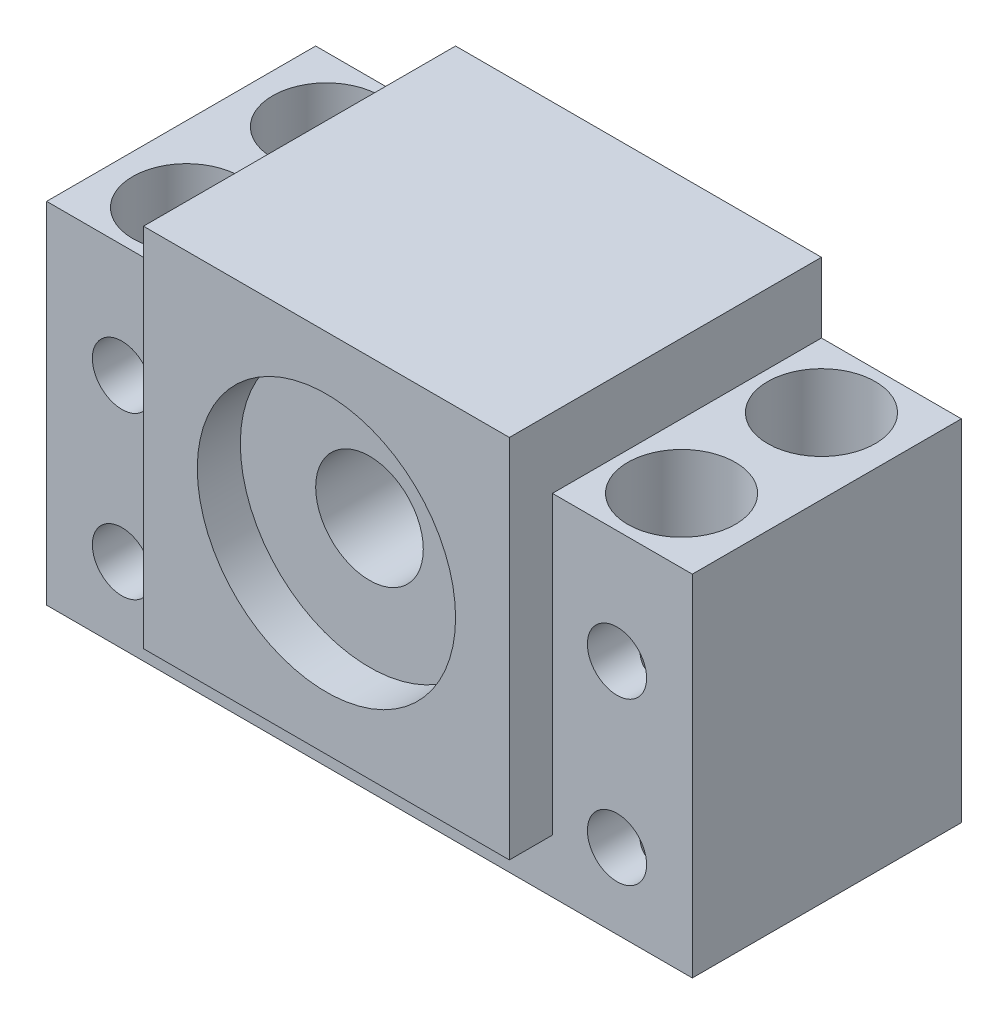
SolidWorks part; units mm, degrees
ref_plane "Спереди" through (0, 0, 0) normal (0, 0, 1) x (1, 0, 0)
ref_plane "Сверху" through (0, 0, 0) normal (0, 1, 0) x (1, 0, 0)
ref_plane "Справа" through (0, 0, 0) normal (1, 0, 0) x (0, 0, -1)
sketch "Эскиз1" plane through (0, 0, 0) normal (0, 0, 1) x (1, 0, 0)
  line L1 (0, 0) -> (60, 0)
  line L2 (0, 0) -> (0, 32.5)
  line L3 (0, 32.5) -> (60, 32.5)
  line L4 (60, 0) -> (60, 32.5)
  dimension "D1" = 32.5
  dimension "D2" = 60
extrude "Бобышка-Вытянуть1" add sketch "Эскиз1" along normal blind 25
sketch "Эскиз2" plane through (0, 0, 25) normal (0, 0, 1) x (1, 0, 0)
  line L0 (30, 0) -> (30, 41.6378) construction
  line L1 (13, 5) -> (47, 5)
  line L2 (13, 5) -> (13, 39)
  line L3 (13, 39) -> (47, 39)
  line L4 (47, 5) -> (47, 39)
  line L5 (0, 0) -> (60, 0) construction
  point P8 (30, 5)
  dimension "D1" = 39
  dimension "D2" = 34
extrude "Бобышка-Вытянуть2" add sketch "Эскиз2" against normal up to surface (25 mm away) up to face at (30, 16.25, 0)
extrude "Бобышка-Вытянуть3" add sketch "Эскиз2<2>" along normal blind 42
sketch "Эскиз2<2>" plane through (0, 0, 25) normal (0, 0, 1) x (1, 0, 0) same geometry as "Эскиз2"
sketch "Эскиз3" plane through (47, 0, 0) normal (1, 0, 0) x (0, 0, -1)
  line L0 (-67, 5) -> (-67, 39) construction
  line L1 (-67, 39) -> (-29, 39)
  line L2 (-67, 39) -> (-67, 5)
  line L3 (-67, 5) -> (-29, 5)
  line L4 (-29, 39) -> (-29, 5)
  line L5 (-67, 5) -> (-25, 5) construction
  line L6 (0, 39) -> (-67, 39) construction
  line L7 (0, 32.5) -> (0, 39) construction
  point P12 (0, 35.75)
  dimension "D1" = 29
extrude "Вырез-Вытянуть1" cut sketch "Эскиз3" against normal through all
sketch "Эскиз4" plane through (0, 0, 25) normal (0, 0, 1) x (1, 0, 0)
  line L0 (0, 22) -> (60, 22) construction
  line L1 (0, 32.5) -> (0, 0) construction
  line L2 (60, 0) -> (60, 32.5) construction
  line L3 (0, 0) -> (60, 0) construction
  line L4 (0, 7) -> (60, 7) construction
  line L5 (30, 39) -> (30, 0) construction
  line L6 (13, 39) -> (47, 39) construction
  line L7 (7, 32.5) -> (7, 0) construction
  line L8 (13, 32.5) -> (0, 32.5) construction
  line L9 (53, 32.5) -> (53, 0) construction
  line L10 (60, 32.5) -> (47, 32.5) construction
  circle A0 centre (7, 22) radius 2.75
  circle A1 centre (7, 7) radius 2.75
  circle A2 centre (53, 7) radius 2.75
  circle A3 centre (53, 22) radius 2.75
  dimension "D4" = 5.5
  dimension "D1" = 22
  dimension "D2" = 15
  dimension "D3" = 46
extrude "Вырез-Вытянуть2" cut sketch "Эскиз4" against normal through all
sketch "Эскиз5" plane through (0, 32.5, 0) normal (0, 1, 0) x (1, 0, 0)
  line L0 (4.25, -25) -> (9.75, -25) construction
  line L1 (4.25, -25) -> (9.75, -25) construction
  line L2 (50.25, -25) -> (55.75, -25) construction
  line L3 (50.25, -25) -> (55.75, -25) construction
  line L4 (7, -25) -> (7, 0) construction
  line L5 (13, 0) -> (0, 0) construction
  line L6 (53, -25) -> (53, 0) construction
  line L7 (0, -6) -> (60, -6) construction
  line L8 (0, -25) -> (0, 0) construction
  line L9 (60, -25) -> (60, 0) construction
  line L10 (0, -19) -> (60, -19) construction
  line L11 (9.75, -25) -> (9.75, 0) construction
  line L12 (50.25, -25) -> (50.25, 0) construction
  line L13 (60, 0) -> (47, 0) construction
  circle A0 centre (7, -19) radius 2.75
  circle A1 centre (7, -6) radius 2.75
  circle A2 centre (53, -6) radius 2.75
  circle A3 centre (53, -19) radius 2.75
  dimension "D1" = 6
  dimension "D2" = 13
extrude "Вырез-Вытянуть3" cut sketch "Эскиз5" against normal through all
sketch "Эскиз6" plane through (0, 32.5, 0) normal (0, 1, 0) x (1, 0, 0)
  circle A0 centre (7, -6) radius 5
  circle A1 centre (7, -19) radius 5
  circle A3 centre (53, -19) radius 5
  circle A4 centre (53, -6) radius 5
  dimension "D1" = 10
extrude "Вырез-Вытянуть4" cut sketch "Эскиз6" against normal blind 7.5
sketch "Эскиз7" plane through (0, 0, 29) normal (0, 0, 1) x (1, 0, 0)
  line L0 (30, 39) -> (30, 5) construction
  line L1 (13, 39) -> (47, 39) construction
  line L2 (13, 5) -> (47, 5) construction
  line L3 (0, 0) -> (60, 0) construction
  circle A0 centre (30, 22) radius 5
  point P10 (30, 0)
  dimension "D1" = 22
  dimension "D2" = 10
extrude "Вырез-Вытянуть5" cut sketch "Эскиз7" against normal through all
sketch "Эскиз8" plane through (0, 0, 29) normal (0, 0, 1) x (1, 0, 0)
  circle A1 centre (30, 22) radius 12
  dimension "D1" = 24
extrude "Вырез-Вытянуть6" cut sketch "Эскиз8" against normal up to surface (4 mm away) up to face at (9.75, 7, 25)
